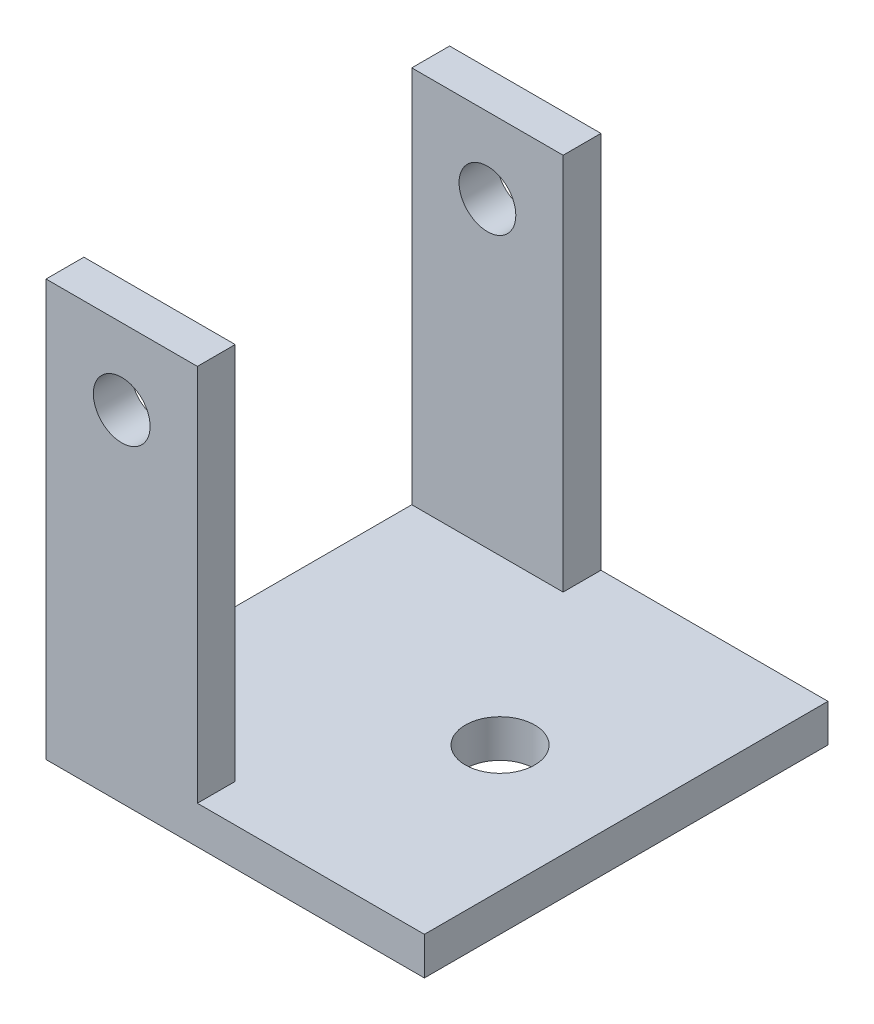
SolidWorks part; units mm, degrees
ref_plane "Front Plane" through (0, 0, 0) normal (0, 0, 1) x (1, 0, 0)
ref_plane "Top Plane" through (0, 0, 0) normal (0, 1, 0) x (1, 0, 0)
ref_plane "Right Plane" through (0, 0, 0) normal (1, 0, 0) x (0, 0, -1)
sketch "Sketch1" plane through (0, 0, 0) normal (0, 0, 1) x (1, 0, 0)
  line L1 (0, 0) -> (12, 0)
  line L2 (0, 0) -> (0, 30)
  line L3 (0, 30) -> (12, 30)
  line L4 (12, 0) -> (12, 30)
  line L5 (0, 0) -> (30, 0)
  line L6 (0, 0) -> (0, -3)
  line L7 (0, -3) -> (30, -3)
  line L8 (30, 0) -> (30, -3)
  dimension "D1" = 12
  dimension "D2" = 30
  dimension "D3" = 3
  dimension "D4" = 30
extrude "Boss-Extrude1" add sketch "Sketch1" along normal blind 3 contours L1 L4 L3 L2 | L8 L5 L1 L6 L7 region at (6, 15, 0) region at (15, -1.5, 0)
extrude "Boss-Extrude2" add sketch "Sketch1<3>" against normal blind 13 contours L8 L5 L1 L6 L7 region at (15, -1.5, 0)
sketch "Sketch1<3>" plane through (0, 0, 0) normal (0, 0, 1) x (1, 0, 0) same geometry as "Sketch1"
mirror "Mirror1" about plane through (0, 0, -13) normal (0, 0, 1) of bodies 102
hole_wizard "M5 Clearance Hole1" positions "Sketch2" profile "Sketch3" hole size "M5" standard "ANSI Metric" end condition through all
sketch "Sketch2" plane through (0, 0, 0) normal (0, 1, 0) x (1, 0, 0)
  line L0 (0, 26) -> (0, 0) construction
  point P0 (20, 13)
  point P5 (0, 13)
  dimension "D1" = 20
sketch "Sketch3" plane through (20, 0, -13) normal (1, 0, 0) x (0, 0, 1)
  line L0 (0, 0) -> (0, 3)
  line L1 (0, 3) -> (2.75, 3)
  line L2 (2.75, 3) -> (2.75, 0)
  line L5 (2.75, 0) -> (0, 0)
  line L11 (0, -6.35) -> (0, 107.95) construction
  dimension "Thru Hole Dia." = 5.5
  dimension "Thru Hole Depth" = 3
hole_wizard "M4 Clearance Hole1" positions "Sketch4" profile "Sketch5" hole size "M4" standard "ANSI Metric" end condition through all
sketch "Sketch4" plane through (0, 0, 3) normal (0, 0, 1) x (1, 0, 0)
  line L0 (0, 30) -> (12, 30) construction
  point P0 (6, 24)
  point P6 (6, 30)
  dimension "D1" = 6
sketch "Sketch5" plane through (6, 24, 3) normal (1, 0, 0) x (0, -1, 0)
  line L0 (0, 0) -> (0, 32)
  line L1 (0, 32) -> (2.25, 32)
  line L2 (2.25, 32) -> (2.25, 0)
  line L5 (2.25, 0) -> (0, 0)
  line L11 (0, -6.35) -> (0, 107.95) construction
  dimension "Thru Hole Dia." = 4.5
  dimension "Thru Hole Depth" = 32
